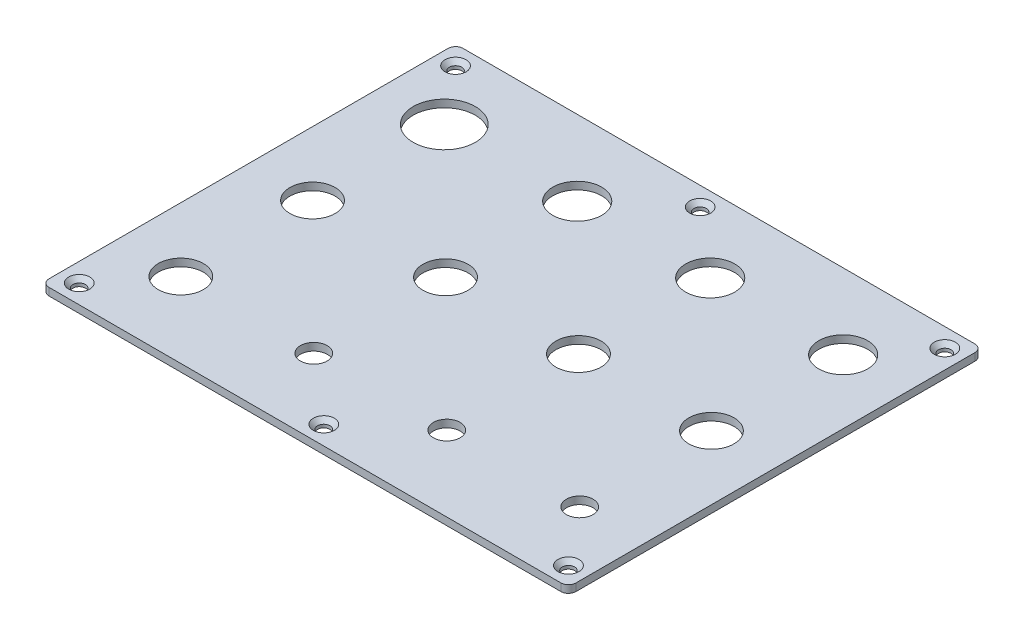
SolidWorks part; units mm, degrees
ref_plane "Front Plane" through (0, 0, 0) normal (0, 0, 1) x (1, 0, 0)
ref_plane "Top Plane" through (0, 0, 0) normal (0, 1, 0) x (1, 0, 0)
ref_plane "Right Plane" through (0, 0, 0) normal (1, 0, 0) x (0, 0, -1)
sketch "Bottom Plate" plane through (0, 0, 0) normal (0, 1, 0) x (1, 0, 0)
  line L1 (0, 0) -> (-140, 0)
  line L2 (0, 0) -> (0, 110)
  line L3 (0, 110) -> (-140, 110)
  line L4 (-140, 0) -> (-140, 110)
  dimension "D1" = 140
  dimension "D2" = 110
extrude "Bottom Plate EXT" add sketch "Bottom Plate" along normal blind 2
sketch "Middle Row" plane through (0, 2, 0) normal (0, 1, 0) x (1, 0, 0)
  line L0 (-140, 110) -> (-140, 0) construction
  line L1 (-140, 55) -> (0, 55) construction
  line L2 (0, 0) -> (0, 110) construction
  circle A0 centre (-123, 55) radius 6
  circle A1 centre (-87.6667, 55) radius 6
  circle A2 centre (-52.3333, 55) radius 6
  circle A3 centre (-17, 55) radius 6
  dimension "D1" = 12
  dimension "D2" = 35.3333
  dimension "D6" = 35.3333
  dimension "D3" = 35.3333
  dimension "D4" = 17
extrude "Middle Row Cut" cut sketch "Middle Row" against normal through all
sketch "Top Row" plane through (0, 2, 0) normal (0, 1, 0) x (1, 0, 0)
  line L0 (0, 0) -> (0, 110) construction
  line L1 (-140, 110) -> (-140, 0) construction
  line L2 (-123, 90) -> (-17, 90) construction
  line L3 (0, 110) -> (-140, 110) construction
  line L7 (-58.8333, 90) -> (-17, 90) construction
  circle A0 centre (-123, 90) radius 8.25
  circle A1 centre (-87.6667, 90) radius 6.5
  circle A2 centre (-52.3333, 90) radius 6.5
  circle A3 centre (-17, 90) radius 6.5
  dimension "D1" = 16.5
  dimension "D2" = 20
  dimension "D7" = 13
  dimension "D8" = 35.3333
  dimension "D3" = 17
  dimension "D4" = 35.3333
  dimension "D5" = 106
  dimension "D6" = 17
extrude "Top Row Cut" cut sketch "Top Row" against normal through all
sketch "Bottom Row" plane through (0, 2, 0) normal (0, 1, 0) x (1, 0, 0)
  line L0 (-140, 0) -> (0, 0) construction
  line L1 (-140, 110) -> (-140, 0) construction
  circle A0 centre (-87.6667, 20) radius 3.55
  circle A1 centre (-52.3333, 20) radius 3.55
  circle A2 centre (-17, 20) radius 3.55
  circle A5 centre (-123, 20) radius 6
  circle A6 centre (-123, 55) radius 6 construction
  dimension "D1" = 7.1
  dimension "D2" = 20
  dimension "D3" = 35.3333
  dimension "D4" = 35.3333
  dimension "D5" = 35.3333
  dimension "D6" = 17
extrude "Bottom Row Cut" cut sketch "Bottom Row" against normal through all
sketch "Plate Screws" plane through (0, 2, 0) normal (0, 1, 0) x (1, 0, 0)
  line L0 (0, 110) -> (-140, 110) construction
  line L1 (-140, 110) -> (-140, 0) construction
  line L2 (-140, 0) -> (0, 0) construction
  line L3 (0, 0) -> (0, 110) construction
  line L4 (-70, 110) -> (-70, 59.8221) construction
  line L5 (0, 55) -> (-30.2044, 55) construction
  circle A0 centre (-135, 105) radius 1.65
  circle A1 centre (-5, 105) radius 1.65
  circle A2 centre (-5, 5) radius 1.65
  circle A3 centre (-135, 5) radius 1.65
  circle A4 centre (-70, 105) radius 1.65
  circle A5 centre (-70, 5) radius 1.65
  dimension "D1" = 3.3
  dimension "D2" = 5
  dimension "D3" = 5
  dimension "D4" = 5
  dimension "D5" = 5
extrude "Plate Screws Cut" cut sketch "Plate Screws" against normal through all
sketch "Plate Screw Head" plane through (0, 2, 0) normal (0, 1, 0) x (1, 0, 0)
  line L0 (-70, 110) -> (-70, 73.7034) construction
  line L1 (0, 110) -> (-140, 110) construction
  line L2 (0, 55) -> (-52.6177, 55) construction
  line L3 (0, 0) -> (0, 110) construction
  circle A0 centre (-135, 105) radius 2.8
  circle A1 centre (-5, 105) radius 2.8
  circle A2 centre (-5, 5) radius 2.8
  circle A3 centre (-135, 5) radius 2.8
  circle A4 centre (-70, 105) radius 2.8
  circle A5 centre (-70, 5) radius 2.8
  dimension "D1" = 5.6
extrude "Plate Screw Head Cut" cut sketch "Plate Screw Head" against normal blind 2 draft 45
fillet "Fillet1" radius 2 1 edges at (-140, 1, -110) type face fillet first side face at (-140, 1, -55) second side face at (-70, 1, -110)
fillet "Fillet2" radius 2 1 edges at (0, 1, -110) type face fillet first side face at (-69, 1, -110) second side face at (0, 1, -55)
fillet "Fillet3" radius 2 1 edges at (0, 1, 0) type face fillet first side face at (0, 1, -54) second side face at (-70, 1, 0)
fillet "Fillet4" radius 2 1 edges at (-140, 1, 0) type face fillet first side face at (-71, 1, 0) second side face at (-140, 1, -54)
equation "\"SPACER_THIRD\"= \"D5@Top Row\" / 3mm"
equation "\"D4@Top Row\"=\"SPACER_THIRD\""
equation "\"D8@Top Row\"=\"SPACER_THIRD\""
equation "\"SPACER_SIDE\"= 17mm"
equation "\"D3@Top Row\" = \"SPACER_SIDE\""
equation "\"D6@Top Row\" = \"SPACER_SIDE\""
equation "\"D4@Middle Row\" = \"SPACER_SIDE\""
equation "\"D2@Middle Row\"=\"SPACER_THIRD\""
equation "\"D3@Middle Row\"=\"SPACER_THIRD\""
equation "\"D6@Middle Row\"=\"SPACER_THIRD\""
equation "\"D6@Bottom Row\" = \"SPACER_SIDE\""
equation "\"D5@Bottom Row\"=\"SPACER_THIRD\""
equation "\"D3@Bottom Row\"=\"SPACER_THIRD\""
equation "\"D4@Bottom Row\"=\"SPACER_THIRD\""
equation "\"SPACER_TOP\"= 20mm"
equation "\"D2@Top Row\"=\"SPACER_TOP\""
equation "\"D2@Bottom Row\"=\"SPACER_TOP\""
equation "\"BUTTON_METAL\"=16.5"
equation "\"BUTTON_PUSH\"=13"
equation "\"D1@Top Row\"=\"BUTTON_METAL\""
equation "\"D7@Top Row\"=\"BUTTON_PUSH\""
